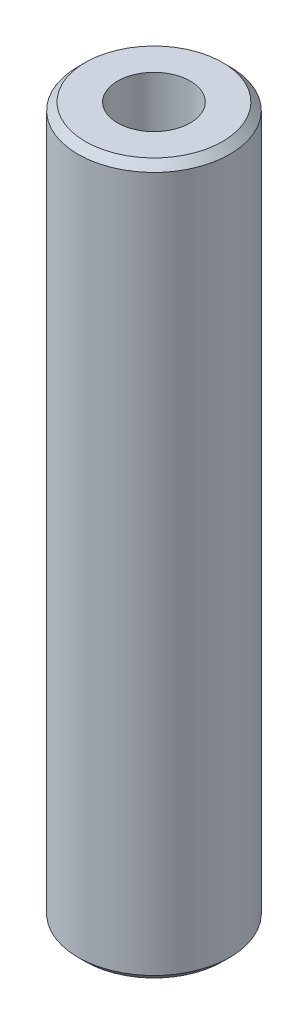
SolidWorks part; units mm, degrees
ref_plane "Front Plane" through (0, 0, 0) normal (0, 0, 1) x (1, 0, 0)
ref_plane "Top Plane" through (0, 0, 0) normal (0, 1, 0) x (1, 0, 0)
ref_plane "Right Plane" through (0, 0, 0) normal (1, 0, 0) x (0, 0, -1)
sketch "Sketch1" plane through (0, 0, 0) normal (0, 1, 0) x (1, 0, 0)
  circle A0 centre (0, 0) radius 12.5
  dimension "SHAFT_OD" = 25
extrude "Boss-Extrude1" add sketch "Sketch1" along normal blind 116.9313
sketch "Sketch2" plane through (0, 0, 0) normal (0, 1, 0) x (1, 0, 0)
  circle A0 centre (0, 0) radius 5.9841
  dimension "BORE_D" = 11.9682
extrude "Cut-Extrude1" cut sketch "Sketch2" along normal through all
chamfer "Chamfer1" distance 1.2107 angle 45 2 edges at (0, 116.9313, 12.5) (0, 0, 12.5)
